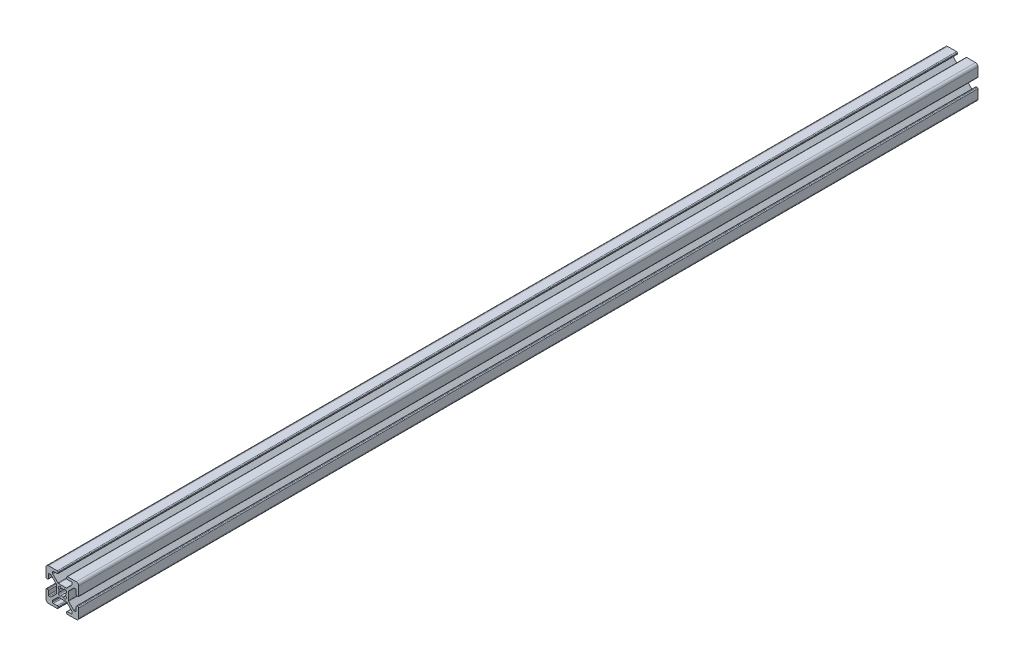
SolidWorks part; units mm, degrees
ref_plane "Front Plane" through (0, 0, 0) normal (0, 0, 1) x (1, 0, 0)
ref_plane "Top Plane" through (0, 0, 0) normal (0, 1, 0) x (1, 0, 0)
ref_plane "Right Plane" through (0, 0, 0) normal (1, 0, 0) x (0, 0, -1)
sketch "Sketch1" plane through (0, 0, 0) normal (0, 0, 1) x (1, 0, 0)
  line L0 (-5.0323, -0.3411) -> (-5.5163, -0.3411)
  line L1 (-6.0243, 0.1669) -> (-6.0243, 2.5159)
  line L2 (-4.5243, 0.1669) -> (-4.5243, 5.5289)
  line L3 (-10.8693, -5.355) -> (-10.8693, -0.5871)
  line L4 (-7.2582, 3.0239) -> (-6.5323, 3.0239)
  line L5 (-7.6174, 2.8752) -> (-10.7205, -0.2279)
  line L6 (-5.0323, -5.6011) -> (-5.5163, -5.6011)
  line L7 (-4.5243, -6.1091) -> (-4.5243, -11.4711)
  line L8 (-6.0243, -6.1091) -> (-6.0243, -8.4581)
  line L9 (-7.2582, -8.9661) -> (-6.5323, -8.9661)
  line L10 (-7.6174, -8.8173) -> (-10.7205, -5.7142)
  line L11 (-12.3994, -5.2756) -> (-12.2198, -5.096)
  line L12 (-17.1543, 6.5209) -> (-17.1543, 6.0369)
  line L13 (-17.6623, 7.0289) -> (-23.0243, 7.0289)
  line L14 (-17.6623, 5.5289) -> (-20.0113, 5.5289)
  line L15 (-12.1404, 0.6839) -> (-16.9082, 0.6839)
  line L16 (-20.5193, 4.295) -> (-20.5193, 5.0209)
  line L17 (-20.3705, 3.9358) -> (-17.2674, 0.8327)
  line L18 (-11.8943, 6.5209) -> (-11.8943, 6.0369)
  line L19 (-11.3863, 7.0289) -> (-6.0243, 7.0289)
  line L20 (-11.3863, 5.5289) -> (-9.0373, 5.5289)
  line L21 (-8.5293, 4.295) -> (-8.5293, 5.0209)
  line L22 (-8.6781, 3.9358) -> (-11.7812, 0.8327)
  line L23 (-12.2198, -0.8462) -> (-12.3994, -0.6666)
  line L24 (-24.0163, -5.6011) -> (-23.5323, -5.6011)
  line L25 (-24.5243, -6.1091) -> (-24.5243, -11.4711)
  line L26 (-23.0243, -6.1091) -> (-23.0243, -8.4581)
  line L27 (-18.1793, -0.5871) -> (-18.1793, -5.355)
  line L28 (-21.7904, -8.9661) -> (-22.5163, -8.9661)
  line L29 (-21.4312, -8.8173) -> (-18.3281, -5.7142)
  line L30 (-24.0163, -0.3411) -> (-23.5323, -0.3411)
  line L31 (-24.5243, 0.1669) -> (-24.5243, 5.5289)
  line L32 (-23.0243, 0.1669) -> (-23.0243, 2.5159)
  line L33 (-21.7904, 3.0239) -> (-22.5163, 3.0239)
  line L34 (-21.4312, 2.8752) -> (-18.3281, -0.2279)
  line L35 (-16.6492, -0.6666) -> (-16.8288, -0.8462)
  line L36 (-11.8943, -12.4631) -> (-11.8943, -11.9791)
  line L37 (-11.3863, -12.9711) -> (-6.0243, -12.9711)
  line L38 (-11.3863, -11.4711) -> (-9.0373, -11.4711)
  line L39 (-16.9082, -6.6261) -> (-12.1404, -6.6261)
  line L40 (-8.5293, -10.2371) -> (-8.5293, -10.9631)
  line L41 (-8.6781, -9.8779) -> (-11.7812, -6.7748)
  line L42 (-17.1543, -12.4631) -> (-17.1543, -11.9791)
  line L43 (-17.6623, -12.9711) -> (-23.0243, -12.9711)
  line L44 (-17.6623, -11.4711) -> (-20.0113, -11.4711)
  line L45 (-20.5193, -10.2371) -> (-20.5193, -10.9631)
  line L46 (-20.3705, -9.8779) -> (-17.2674, -6.7748)
  line L47 (-16.8288, -5.096) -> (-16.6492, -5.2756)
  arc A0 (-15.3283, -4.9062) -> (-13.7203, -4.9062) centre (-14.5243, -2.9711) ccw
  arc A1 (-6.0243, 2.5159) -> (-6.5323, 3.0239) centre (-6.5323, 2.5159) ccw
  arc A2 (-7.2582, 3.0239) -> (-7.6174, 2.8752) centre (-7.2582, 2.5159) ccw
  arc A3 (-10.7205, -0.2279) -> (-10.8693, -0.5871) centre (-10.3613, -0.5871) ccw
  arc A4 (-10.8693, -5.355) -> (-10.7205, -5.7142) centre (-10.3613, -5.355) ccw
  arc A5 (-7.6174, -8.8173) -> (-7.2582, -8.9661) centre (-7.2582, -8.4581) ccw
  arc A6 (-6.5323, -8.9661) -> (-6.0243, -8.4581) centre (-6.5323, -8.4581) ccw
  arc A7 (-5.5163, -5.6011) -> (-6.0243, -6.1091) centre (-5.5163, -6.1091) ccw
  arc A8 (-4.5243, -6.1091) -> (-5.0323, -5.6011) centre (-5.0323, -6.1091) ccw
  arc A9 (-5.0323, -0.3411) -> (-4.5243, 0.1669) centre (-5.0323, 0.1669) ccw
  arc A10 (-6.0243, 0.1669) -> (-5.5163, -0.3411) centre (-5.5163, 0.1669) ccw
  arc A11 (-13.7203, -4.9062) -> (-12.3994, -5.2756) centre (-12.9559, -4.7191) ccw
  arc A12 (-12.2198, -5.096) -> (-12.5892, -3.775) centre (-12.7763, -4.5395) ccw
  arc A13 (-17.1543, 6.5209) -> (-17.6623, 7.0289) centre (-17.6623, 6.5209) ccw
  arc A14 (-17.6623, 5.5289) -> (-17.1543, 6.0369) centre (-17.6623, 6.0369) ccw
  arc A15 (-12.5892, -3.775) -> (-12.5892, -2.1671) centre (-14.5243, -2.9711) ccw
  arc A16 (-17.2674, 0.8327) -> (-16.9082, 0.6839) centre (-16.9082, 1.1919) ccw
  arc A17 (-20.0113, 5.5289) -> (-20.5193, 5.0209) centre (-20.0113, 5.0209) ccw
  arc A18 (-20.5193, 4.295) -> (-20.3705, 3.9358) centre (-20.0113, 4.295) ccw
  arc A19 (-11.8943, 6.0369) -> (-11.3863, 5.5289) centre (-11.3863, 6.0369) ccw
  arc A20 (-11.3863, 7.0289) -> (-11.8943, 6.5209) centre (-11.3863, 6.5209) ccw
  arc A21 (-8.5293, 5.0209) -> (-9.0373, 5.5289) centre (-9.0373, 5.0209) ccw
  arc A22 (-8.6781, 3.9358) -> (-8.5293, 4.295) centre (-9.0373, 4.295) ccw
  arc A23 (-12.1404, 0.6839) -> (-11.7812, 0.8327) centre (-12.1404, 1.1919) ccw
  arc A24 (-12.5892, -2.1671) -> (-12.2198, -0.8462) centre (-12.7763, -1.4027) ccw
  arc A25 (-12.3994, -0.6666) -> (-13.7203, -1.0359) centre (-12.9559, -1.223) ccw
  arc A26 (-24.0163, -5.6011) -> (-24.5243, -6.1091) centre (-24.0163, -6.1091) ccw
  arc A27 (-23.0243, -6.1091) -> (-23.5323, -5.6011) centre (-23.5323, -6.1091) ccw
  arc A28 (-13.7203, -1.0359) -> (-15.3283, -1.0359) centre (-14.5243, -2.9711) ccw
  arc A29 (-18.3281, -5.7142) -> (-18.1793, -5.355) centre (-18.6873, -5.355) ccw
  arc A30 (-23.0243, -8.4581) -> (-22.5163, -8.9661) centre (-22.5163, -8.4581) ccw
  arc A31 (-21.7904, -8.9661) -> (-21.4312, -8.8173) centre (-21.7904, -8.4581) ccw
  arc A32 (-23.5323, -0.3411) -> (-23.0243, 0.1669) centre (-23.5323, 0.1669) ccw
  arc A33 (-24.5243, 0.1669) -> (-24.0163, -0.3411) centre (-24.0163, 0.1669) ccw
  arc A34 (-22.5163, 3.0239) -> (-23.0243, 2.5159) centre (-22.5163, 2.5159) ccw
  arc A35 (-21.4312, 2.8752) -> (-21.7904, 3.0239) centre (-21.7904, 2.5159) ccw
  arc A36 (-18.1793, -0.5871) -> (-18.3281, -0.2279) centre (-18.6873, -0.5871) ccw
  arc A37 (-15.3283, -1.0359) -> (-16.6492, -0.6666) centre (-16.0927, -1.223) ccw
  arc A38 (-16.8288, -0.8462) -> (-16.4594, -2.1671) centre (-16.2723, -1.4027) ccw
  arc A39 (-11.8943, -12.4631) -> (-11.3863, -12.9711) centre (-11.3863, -12.4631) ccw
  arc A40 (-11.3863, -11.4711) -> (-11.8943, -11.9791) centre (-11.3863, -11.9791) ccw
  arc A41 (-16.4594, -2.1671) -> (-16.4594, -3.775) centre (-14.5243, -2.9711) ccw
  arc A42 (-11.7812, -6.7748) -> (-12.1404, -6.6261) centre (-12.1404, -7.1341) ccw
  arc A43 (-9.0373, -11.4711) -> (-8.5293, -10.9631) centre (-9.0373, -10.9631) ccw
  arc A44 (-8.5293, -10.2371) -> (-8.6781, -9.8779) centre (-9.0373, -10.2371) ccw
  arc A45 (-17.1543, -11.9791) -> (-17.6623, -11.4711) centre (-17.6623, -11.9791) ccw
  arc A46 (-17.6623, -12.9711) -> (-17.1543, -12.4631) centre (-17.6623, -12.4631) ccw
  arc A47 (-20.5193, -10.9631) -> (-20.0113, -11.4711) centre (-20.0113, -10.9631) ccw
  arc A48 (-20.3705, -9.8779) -> (-20.5193, -10.2371) centre (-20.0113, -10.2371) ccw
  arc A49 (-16.9082, -6.6261) -> (-17.2674, -6.7748) centre (-16.9082, -7.1341) ccw
  arc A50 (-16.4594, -3.775) -> (-16.8288, -5.096) centre (-16.2723, -4.5395) ccw
  arc A51 (-16.6492, -5.2756) -> (-15.3283, -4.9062) centre (-16.0927, -4.7191) ccw
  arc A52 (-4.5243, 5.5289) -> (-6.0243, 7.0289) centre (-6.0243, 5.5289) ccw
  arc A53 (-6.0243, -12.9711) -> (-4.5243, -11.4711) centre (-6.0243, -11.4711) ccw
  arc A54 (-24.5243, -11.4711) -> (-23.0243, -12.9711) centre (-23.0243, -11.4711) ccw
  arc A55 (-23.0243, 7.0289) -> (-24.5243, 5.5289) centre (-23.0243, 5.5289) ccw
extrude "Extrude1" add sketch "Sketch1" along normal blind 550
